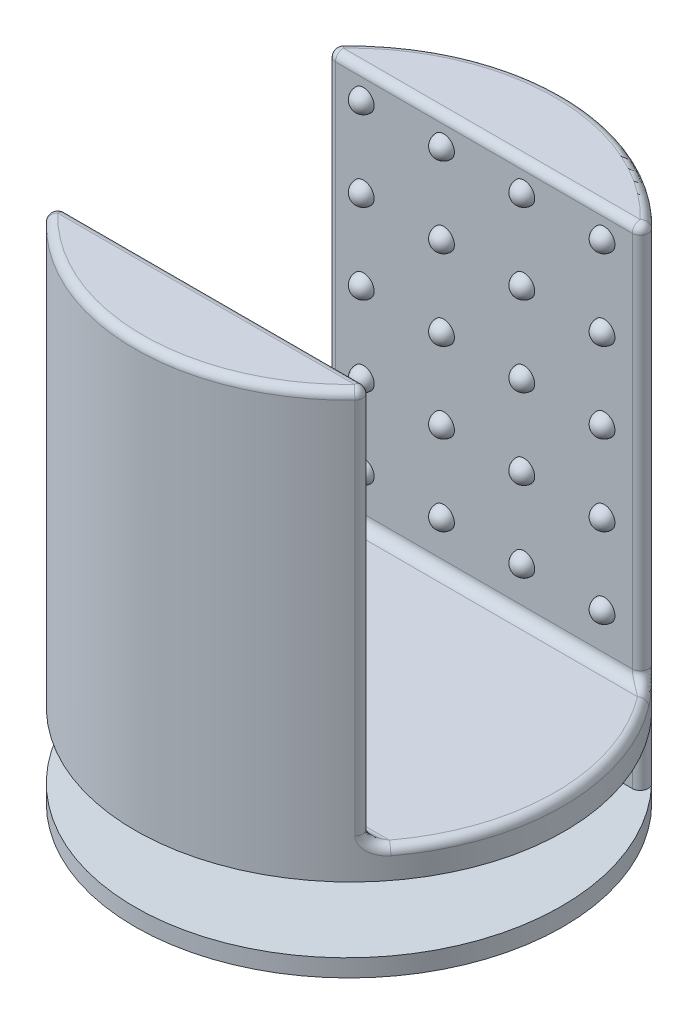
SolidWorks part; units mm, degrees
ref_plane "Front Plane" through (0, 0, 0) normal (0, 0, 1) x (1, 0, 0)
ref_plane "Top Plane" through (0, 0, 0) normal (0, 1, 0) x (1, 0, 0)
ref_plane "Right Plane" through (0, 0, 0) normal (1, 0, 0) x (0, 0, -1)
ref_plane "Plane1" through (-3.75, 0, 0) normal (1, 0, 0) x (0, 0, -1)
sketch "Sketch2" plane through (0, 0, 0) normal (0, 1, 0) x (1, 0, 0)
  line L1 (-35, 12.5) -> (35, 12.5)
  line L2 (-35, 12.5) -> (-35, -12.5)
  line L3 (-35, -12.5) -> (35, -12.5)
  line L4 (35, 12.5) -> (35, -12.5)
  line L5 (-35, 12.5) -> (35, -12.5) construction
  line L6 (-35, -12.5) -> (35, 12.5) construction
  point P0 (0, 0)
  dimension "D1" = 25
  dimension "D2" = 70
sketch "Sketch3" plane through (0, 0, 0) normal (0, 1, 0) x (1, 0, 0)
  circle A0 centre (0, 0) radius 20
  dimension "D1" = 40
extrude "Boss-Extrude1" add sketch "Sketch3" along normal blind 40
sketch "Sketch4" plane through (0, 40, 0) normal (0, 1, 0) x (1, 0, 0)
  line L8 (-35.1, 12.6) -> (-35.1, -12.6)
  line L9 (35.1, 12.6) -> (-35.1, 12.6)
  line L10 (35.1, -12.6) -> (35.1, 12.6)
  line L11 (-35.1, -12.6) -> (35.1, -12.6)
  line L12 (-35.1, 12.6) -> (-35.1, -12.6)
  line L13 (35.1, 12.6) -> (-35.1, 12.6)
  line L14 (35.1, -12.6) -> (35.1, 12.6)
  line L15 (-35.1, -12.6) -> (35.1, -12.6)
  dimension "D1" = 0.1
extrude "Cut-Extrude1" cut sketch "Sketch4" against normal offset from surface (37 mm away) 3 up to face at (0, 0, 20)
sketch "Sketch5" plane through (-3.75, 0, 0) normal (1, 0, 0) x (0, 0, -1)
  line L0 (-12.6, 40) -> (-12.6, 3) construction
  line L1 (-12.6, 40) -> (-12.6, 3) construction
  line L2 (-11.6, 37.5) -> (-13.6, 37.5) construction
  line L3 (-11.6, 37.5) -> (-13.6, 37.5)
  arc A0 (-11.6, 37.5) -> (-13.6, 37.5) centre (-12.6, 37.5) ccw
  point P4 (-12.6, 37.5)
  dimension "D1" = 2.5
  dimension "D2" = 2
revolve "Revolve1" add sketch "Sketch5" angle 360 about L3
pattern_linear "LPattern1" count 3 spacing 7.5 along (1, 0, 0) count 2 spacing 7.5 along (-1, 0, 0) of "Revolve1" pattern seed only yes
pattern_linear "LPattern2" count 5 spacing 7.5 along (0, -1, 0) of "LPattern1"
mirror "Mirror1" about plane through (0, 0, 0) normal (0, 0, 1) of "LPattern2", "LPattern1"
fillet "Fillet3" radius 1 2 edges at (0, 3, 12.6) (0, 3, -12.6)
fillet "Fillet4" radius 0.75 10 edges at (15.6511, 3.4759, -12.4517) (20, 3, 0) (15.7314, 3.3386, 12.35) (-15.7314, 3.3386, -12.35) (-20, 3, 0) (-15.6511, 3.4759, 12.4517) (15.5319, 22, -12.6) (-15.5319, 22, -12.6) (15.5319, 22, 12.6) (-15.5319, 22, 12.6)
fillet "Fillet5" radius 0.75 8 edges at (-14.5588, 40, 13.0564) (0, 40, 12.6) (14.5588, 40, 13.0564) (0, 40, 20) (-14.5588, 40, -13.0564) (0, 40, -20) (14.5588, 40, -13.0564) (0, 40, -12.6)
sketch "Sketch6" plane through (0, 0, 0) normal (0, -1, 0) x (1, 0, 0)
  circle A1 centre (0, 0) radius 20
  circle A2 centre (0, 0) radius 20
  dimension "D1" = 0
extrude "Boss-Extrude2" add sketch "Sketch6" along normal blind 7.5
sketch "Sketch7" plane through (0, 0, 0) normal (1, 0, 0) x (0, 0, -1)
  line L1 (-22.3991, -5.9261) -> (12.6, -5.6761)
  line L2 (-22.3991, -5.9261) -> (-22.3991, 0.3239)
  line L3 (-22.3991, 0.3239) -> (12.6, 0.0739)
  line L4 (12.6, -5.6761) -> (12.6, 0.0739)
  line L5 (-22.3991, -5.9261) -> (12.6, 0.0739) construction
  line L6 (-22.3991, 0.3239) -> (12.6, -5.6761) construction
  line L8 (12.6, -2.8011) -> (-22.3991, -2.8011) construction
  line L9 (12.6, 4) -> (12.6, 39.25) construction
  point P0 (-4.1704, -2.8011)
  dimension "D1" = 5.75
  dimension "D2" = 6.25
  dimension "D3" = 35
  dimension "D4" = 2
extrude "Cut-Extrude2" cut sketch "Sketch7" against normal through all both and the other way through all
sketch "Sketch8" plane through (0, -7.5, 0) normal (0, -1, 0) x (1, 0, 0)
  line L1 (9.75, 15) -> (-9.75, 15)
  line L2 (9.75, 15) -> (9.75, -15)
  line L3 (9.75, -15) -> (-9.75, -15)
  line L4 (-9.75, 15) -> (-9.75, -15)
  line L5 (9.75, 15) -> (-9.75, -15) construction
  line L6 (9.75, -15) -> (-9.75, 15) construction
  point P0 (0, 0)
  dimension "D1" = 19.5
  dimension "D2" = 30
extrude "Cut-Extrude3" cut sketch "Sketch8" against normal blind 0.75
fillet "Fillet7" radius 0.75 2 edges at (-15.5319, -2.8011, -12.6) (15.5319, -2.8011, -12.6)
